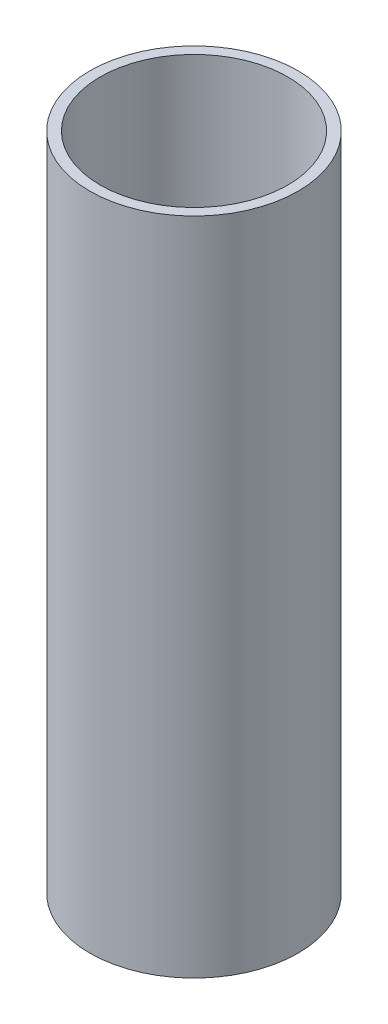
SolidWorks part; units mm, degrees
ref_plane "前视基准面" through (0, 0, 0) normal (0, 0, 1) x (1, 0, 0)
ref_plane "上视基准面" through (0, 0, 0) normal (0, 1, 0) x (1, 0, 0)
ref_plane "右视基准面" through (0, 0, 0) normal (1, 0, 0) x (0, 0, -1)
sketch "草图1" plane through (0, 0, 0) normal (0, 1, 0) x (1, 0, 0)
  line L0 (0, 30) -> (0, -30) construction
  circle A0 centre (0, 0) radius 30
  circle A1 centre (0, 0) radius 27
  dimension "D1" = 60
  dimension "D2" = 54
extrude "凸台-拉伸1" add sketch "草图1" along normal blind 190
ref_axis "基准轴1" through (0, 190, 0) along (0, -1, 0)
ref_plane "基准面2" through (0, 0, 30) normal (0, 0, 1) x (1, 0, 0)
sketch "草图3" plane through (0, 0, 30) normal (0, 0, 1) x (1, 0, 0)
  line L0 (-30, 190) -> (41.7694, 65.6917)
  line L1 (-30, 190) -> (-30, 0) construction
  dimension "D1" = 30
  dimension "D2" = 190
